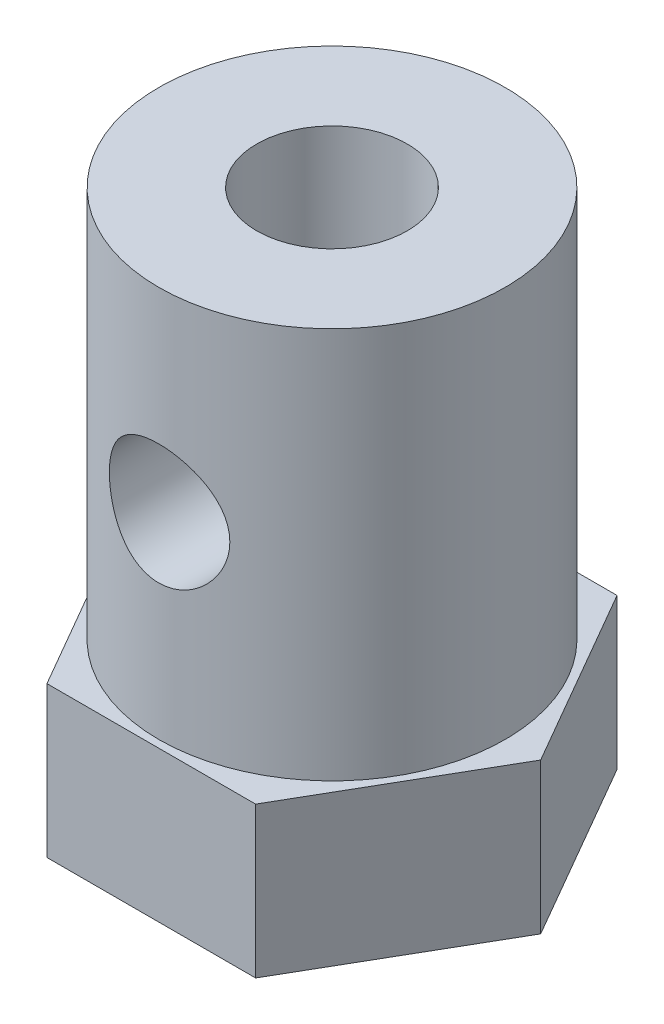
SolidWorks part; units mm, degrees
ref_plane "前视基准面" through (0, 0, 0) normal (0, 0, 1) x (1, 0, 0)
ref_plane "上视基准面" through (0, 0, 0) normal (0, 1, 0) x (1, 0, 0)
ref_plane "右视基准面" through (0, 0, 0) normal (1, 0, 0) x (0, 0, -1)
sketch "草图1" plane through (0, 0, 0) normal (0, 1, 0) x (1, 0, 0)
  line L1 (6.9282, 0) -> (3.4641, 6)
  line L2 (3.4641, 6) -> (-3.4641, 6)
  line L3 (-3.4641, 6) -> (-6.9282, 0)
  line L4 (-6.9282, 0) -> (-3.4641, -6)
  line L5 (-3.4641, -6) -> (3.4641, -6)
  line L6 (3.4641, -6) -> (6.9282, 0)
  circle A0 centre (0, 0) radius 6 construction
  dimension "D1" = 12
extrude "凸台-拉伸1" add sketch "草图1" along normal blind 5
sketch "草图2" plane through (0, 5, 0) normal (0, 1, 0) x (1, 0, 0)
  circle A0 centre (0, 0) radius 5.75
  dimension "D1" = 11.5
extrude "凸台-拉伸2" add sketch "草图2" along normal blind 13
sketch "草图4" plane through (0, 0, 0) normal (0, -1, 0) x (-1, 0, 0)
  circle A0 centre (0, 0) radius 2
  dimension "D1" = 4
extrude "切除-拉伸2" cut sketch "草图4" against normal blind 5
thread "螺纹线1" pitch 0.3175 method extrude profile "螺纹线轮廓1" start angle 0, offset 0, length 5, pitch 0.3175, diameter 4
ref_plane "基准面1" through (2, 0, 0) normal (0, 0, 1) x (1, 0, 0)
sketch "螺纹线轮廓1" plane through (2, 0, 0) normal (0, 0, 1) x (1, 0, 0)
  line L0 (0, 0) -> (0, 0.3175) construction
  line L11 (0, 0) -> (0, 0.2778)
  line L12 (0, 0.2778) -> (-0.1719, 0.1786)
  line L13 (-0.1719, 0.1786) -> (-0.1719, 0.0992)
  line L15 (-0.1719, 0.0992) -> (0, 0)
  line L17 (-0.1719, 0.1389) -> (0, 0.1389) construction
  point P2 (0, 0)
  dimension "Pitch" = 0.3175
  dimension "Profile_Angle" = 60
  dimension "Profile_Land" = 0.0794
  dimension "Profile_Height" = 0.1719
sketch "草图11" plane through (0, 18, 0) normal (0, 1, 0) x (1, 0, 0)
  circle A0 centre (0, 0) radius 2.5
  dimension "D1" = 5
extrude "切除-拉伸3" cut sketch "草图11" against normal blind 13
sketch "草图12" plane through (0, 0, 0) normal (0, 0, 1) x (1, 0, 0)
  line L0 (5.75, 18) -> (-5.75, 18) construction
  circle A0 centre (0, 11.5) radius 2
  point P4 (0, 0)
  dimension "D1" = 4
  dimension "D2" = 6.5
extrude "切除-拉伸5" cut sketch "草图12" against normal blind 13 and the other way blind 13
